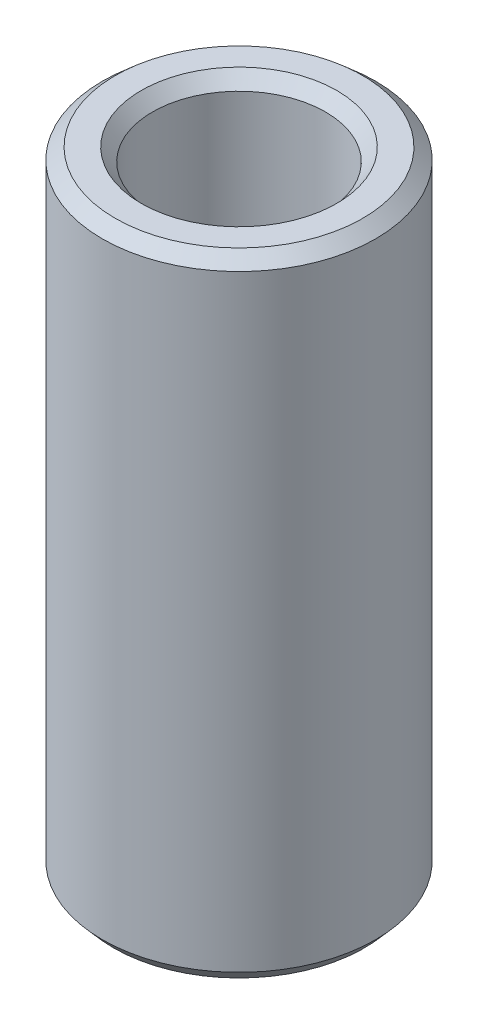
SolidWorks part; units mm, degrees
ref_plane "Front Plane" through (0, 0, 0) normal (0, 0, 1) x (1, 0, 0)
ref_plane "Top Plane" through (0, 0, 0) normal (0, 1, 0) x (1, 0, 0)
ref_plane "Right Plane" through (0, 0, 0) normal (1, 0, 0) x (0, 0, -1)
sketch "Sketch1" plane through (0, 0, 0) normal (0, 1, 0) x (1, 0, 0)
  circle A0 centre (0, 0) radius 47.5
  dimension "SLEEVE_OD" = 95
extrude "Boss-Extrude1" add sketch "Sketch1" along normal blind 219.4409
sketch "Sketch2" plane through (0, 0, 0) normal (0, 1, 0) x (1, 0, 0)
  circle A0 centre (0, 0) radius 30.0786
  dimension "BORE_D" = 60.1572
extrude "Cut-Extrude1" cut sketch "Sketch2" along normal through all
chamfer "Chamfer1" distance 3.9353 angle 48.717 4 edges at (0, 219.4409, 30.0786) (0, 0, 30.0786) (0, 0, 47.5) (0, 219.4409, 47.5) first distance on face at (0, 219.4409, 30.0786) first distance on face at (0, 0, 30.0786) first distance on face at (0, 219.4409, 47.5)
